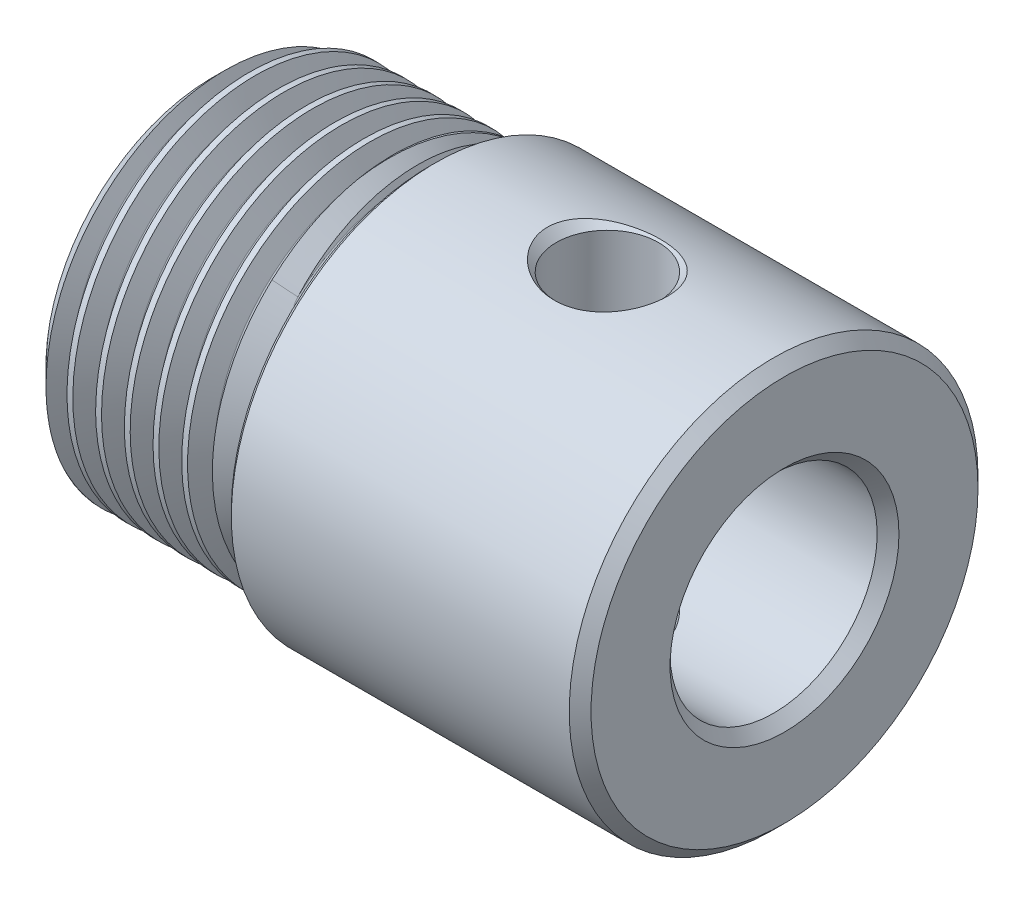
SolidWorks part; units mm, degrees
material "AISI 316 Annealed Stainless Steel Bar (SS)"
ref_plane "Plane1" through (0, 0, 0) normal (0, 0, 1) x (1, 0, 0)
ref_plane "Plane2" through (0, 0, 0) normal (0, 1, 0) x (1, 0, 0)
ref_plane "Plane3" through (0, 0, 0) normal (1, 0, 0) x (0, 0, -1)
sketch "Sketch1" plane through (0, 0, 0) normal (0, 0, 1) x (1, 0, 0)
  line L0 (0, 0) -> (-30.5746, 0) construction
  line L1 (-0.508, 4.826) -> (-26.162, 4.826)
  line L2 (0, 5.334) -> (0, 9.017)
  line L3 (-0.508, 9.525) -> (-16.256, 9.525)
  line L4 (-18.415, 8.636) -> (-17.526, 7.747)
  line L5 (-18.415, 8.636) -> (-25.781, 8.636)
  line L6 (-26.67, 7.747) -> (-26.67, 5.334)
  line L7 (0, 9.017) -> (-0.508, 9.525)
  line L8 (0, 5.334) -> (-0.508, 4.826)
  line L9 (-26.67, 5.334) -> (-26.162, 4.826)
  line L10 (-17.526, 7.747) -> (-16.51, 7.747)
  line L11 (-16.51, 7.747) -> (-16.51, 9.271)
  line L12 (-25.781, 8.636) -> (-26.67, 7.747)
  line L13 (-8.255, -9.525) -> (-8.255, 9.525) construction
  line L14 (-16.256, 9.525) -> (-16.51, 9.271)
  line L15 (-27.5368, 8.636) -> (-27.1169, 7.8294) construction
  line L16 (-26.67, 8.255) -> (-27.3384, 8.255) construction
  line L17 (-27.3384, 8.255) -> (-28.0068, 8.255) construction
  line L18 (-26.8916, 7.8294) -> (-26.4717, 8.636) construction
  line L19 (-26.4717, 8.636) -> (-27.5368, 8.636) construction
  line L20 (-27.0042, 7.613) -> (-27.0042, 9.5313) construction
  arc A0 (-27.1169, 7.8294) -> (-26.8916, 7.8294) centre (-27.0042, 7.888) ccw construction
  point P3 (0, 4.826)
  point P5 (-16.51, 9.525)
  point P6 (0, 9.525)
  point P10 (-26.67, 4.826)
  point P20 (-8.255, 0)
  dimension "D16" = 0.127
  dimension "D1" = 19.05
  dimension "D2" = 9.652
  dimension "D3" = 26.67
  dimension "D4" = 16.51
  dimension "D5" = 8.255
  dimension "D9" = 17.272
  dimension "D10" = 15.494
  dimension "D11" = 1.016
  dimension "D12" = 55
  dimension "D13" = 1.3368
  dimension "D15" = 16.51
revolve "Revolve1" add sketch "Sketch1" angle 360 about L0
sketch "Sketch2" plane through (-26.67, 0, 0) normal (-1, 0, 0) x (0, 0, 1)
  circle A0 centre (0, 0) radius 8.255
curve "Helix/Spiral1" pitch 1.3368 height 9.6921 radius 8.255 centre (-26.67, 0, 0) axis (1, 0, 0) start towards (0, 1, 0)
sketch "Sketch3" plane through (0, 0, 0) normal (0, 0, 1) x (1, 0, 0)
  line L0 (-26.8916, 7.8294) -> (-26.4717, 8.636) construction
  line L1 (-26.4717, 8.636) -> (-27.5368, 8.636) construction
  line L2 (-27.5368, 8.636) -> (-27.1169, 7.8294) construction
  line L3 (-26.8916, 7.8294) -> (-26.4717, 8.636)
  line L4 (-26.4717, 8.636) -> (-27.5368, 8.636)
  line L5 (-27.5368, 8.636) -> (-27.1169, 7.8294)
  arc A0 (-27.1169, 7.8294) -> (-26.8916, 7.8294) centre (-27.0042, 7.888) ccw construction
  arc A1 (-27.1169, 7.8294) -> (-26.8916, 7.8294) centre (-27.0042, 7.888) ccw
sweep "Cut-Sweep1" cut profiles "Sketch3" path "Helix/Spiral1"
sketch "Sketch4" plane through (0, 0, 0) normal (0, 0, 1) x (1, 0, 0)
  line L0 (0, 0) -> (-30.5581, 0) construction
  line L1 (-8.255, 0) -> (-8.255, 19.8489) construction
  line L2 (-0.508, 9.525) -> (-16.256, 9.525) construction
  line L3 (-8.255, 9.525) -> (-5.461, 9.525)
  line L4 (-5.461, 9.525) -> (-5.8738, 9.1122)
  line L5 (-5.8738, 9.1122) -> (-5.8737, -9.1122)
  line L6 (-5.461, -9.525) -> (-5.8737, -9.1122)
  line L7 (-8.255, -9.525) -> (-5.461, -9.525)
  line L8 (-8.255, -9.525) -> (-8.255, 9.525) construction
  line L9 (-0.508, 9.525) -> (-16.256, 9.525) construction
  line L10 (-8.255, 9.525) -> (-8.255, -9.525)
  point P11 (-5.8737, 0)
  dimension "D1" = 4.7625
  dimension "D2" = 45
  dimension "D3" = 5.588
revolve "Cut-Revolve1" cut sketch "Sketch4" angle 360 about L1
